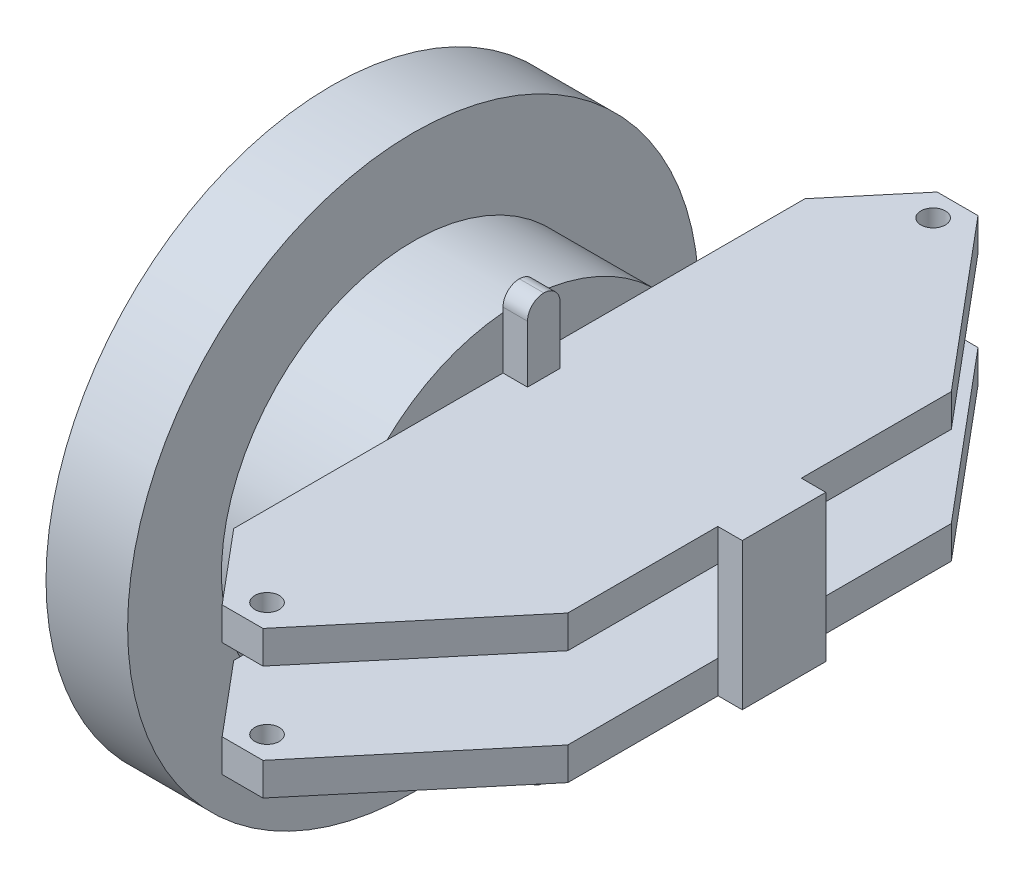
SolidWorks part; units mm, degrees
ref_plane "Front Plane" through (0, 0, 0) normal (0, 0, 1) x (1, 0, 0)
ref_plane "Top Plane" through (0, 0, 0) normal (0, 1, 0) x (1, 0, 0)
ref_plane "Right Plane" through (0, 0, 0) normal (1, 0, 0) x (0, 0, -1)
sketch "Sketch1" plane through (0, 0, 0) normal (1, 0, 0) x (0, 0, -1)
  circle A0 centre (0, 0) radius 35
  dimension "D1" = 70
extrude "Boss-Extrude1" add sketch "Sketch1" along normal blind 10
sketch "Sketch2" plane through (10, 0, 0) normal (1, 0, 0) x (0, 0, -1)
  circle A0 centre (0, 0) radius 23.5
  dimension "D1" = 47
extrude "Boss-Extrude2" add sketch "Sketch2" along normal blind 13
ref_plane "Plane1" through (0, 13, 0) normal (0, 1, 0) x (1, 0, 0)
sketch "Sketch3" plane through (0, 13, 0) normal (0, 1, 0) x (1, 0, 0)
  line L0 (23, 35) -> (23, -35)
  line L1 (23, -23.5) -> (23, 23.5) construction
  line L2 (23, -35) -> (30.3921, -43.8095)
  line L3 (30.3921, -43.8095) -> (35.3921, -43.8095)
  line L4 (35.3921, -43.8095) -> (52.4335, -23.5004)
  line L5 (23, -35) -> (55.6961, -35) construction
  line L6 (35.3921, -43.8095) -> (44.5371, -43.8095) construction
  line L7 (52.4335, -23.5004) -> (52.4335, 23.5004)
  line L8 (23, 0) -> (51.8003, 0) construction
  line L9 (23, 35) -> (52.4335, 23.5004) construction
  line L10 (35.3921, 43.8095) -> (44.5371, 43.8095) construction
  line L11 (35.3921, 43.8095) -> (52.4335, 23.5004)
  line L12 (30.3921, 43.8095) -> (35.3921, 43.8095)
  line L13 (23, 35) -> (30.3921, 43.8095)
  line L14 (23, -23.5) -> (49.3135, -23.5) construction
  line L15 (10, -23.5) -> (23, -23.5) construction
  point P15 (52.4335, 0)
  dimension "D1" = 35
  dimension "D2" = 11.5
  dimension "D3" = 40
  dimension "D4" = 5
  dimension "D5" = 50
extrude "Boss-Extrude4" add sketch "Sketch3" along normal blind 4
sketch "Sketch5" plane through (0, 17, 0) normal (0, 1, 0) x (1, 0, 0)
  line L0 (30.3921, -43.8095) -> (35.3921, -43.8095) construction
  line L1 (35.3921, 43.8095) -> (30.3921, 43.8095) construction
  circle A0 centre (32.8921, -40.8095) radius 1.5
  circle A1 centre (32.8921, 40.8095) radius 1.5
  point P8 (32.8921, 43.8095)
  dimension "D2" = 3
  dimension "D3" = 3
  dimension "D1" = 3
  dimension "D4" = 3
extrude "Cut-Extrude1" cut sketch "Sketch5" against normal through all both and the other way through all
sketch "Sketch6" plane through (23, 0, 0) normal (1, 0, 0) x (0, 0, -1)
  line L0 (0, 17) -> (0, 23.5) construction
  line L1 (-23.5004, 17) -> (23.5004, 17) construction
  line L2 (-2, 17) -> (-2, 26)
  line L3 (16.225, 17) -> (-16.225, 17) construction
  line L4 (-2, 26) -> (2, 26)
  line L5 (2, 26) -> (2, 17)
  line L6 (2, 17) -> (-2, 17)
  arc A0 (16.225, 17) -> (-16.225, 17) centre (0, 0) ccw construction
  dimension "D1" = 9
  dimension "D2" = 2
  dimension "D3" = 2
extrude "Boss-Extrude5" add sketch "Sketch6" along normal blind 3
fillet "Fillet1" radius 2 2 edges at (24.5, 26, -2) (24.5, 26, 2)
mirror "Mirror2" about plane through (0, 0, 0) normal (0, 1, 0) of "Fillet1", "Boss-Extrude5"
sketch "Sketch8" plane through (0, 0, 0) normal (-1, 0, 0) x (0, 0, 1)
  circle A0 centre (0, 0) radius 10
  dimension "D1" = 20
extrude "Cut-Extrude2" cut sketch "Sketch8" against normal blind 10
ref_plane "Plane2" through (0, 8, 0) normal (0, -1, 0) x (-1, 0, 0)
mirror "Mirror3" about plane through (0, 8, 0) normal (0, -1, 0) of "Cut-Extrude1", "Boss-Extrude4"
sketch "Sketch9" plane through (52.4335, 0, 0) normal (1, 0, 0) x (0, 0, -1)
  point P0 (3.4987, 3.8866)
  point P1 (0, 0)
sketch "Sketch11" plane through (52.4335, 0, 0) normal (1, 0, 0) x (0, 0, -1)
  line L0 (-23.5004, 17) -> (23.5004, 17) construction
  line L1 (5.1175, -0.9615) -> (-5.1175, -0.9615)
  line L2 (5.1175, -0.9615) -> (5.1175, 17)
  line L3 (5.1175, 17) -> (-5.1175, 17)
  line L4 (-5.1175, -0.9615) -> (-5.1175, 17)
  line L5 (5.1175, -0.9615) -> (-5.1175, 17) construction
  line L6 (5.1175, 17) -> (-5.1175, -0.9615) construction
  point P0 (0, 8.0193)
extrude "Boss-Extrude6" add sketch "Sketch11" along normal blind 3
